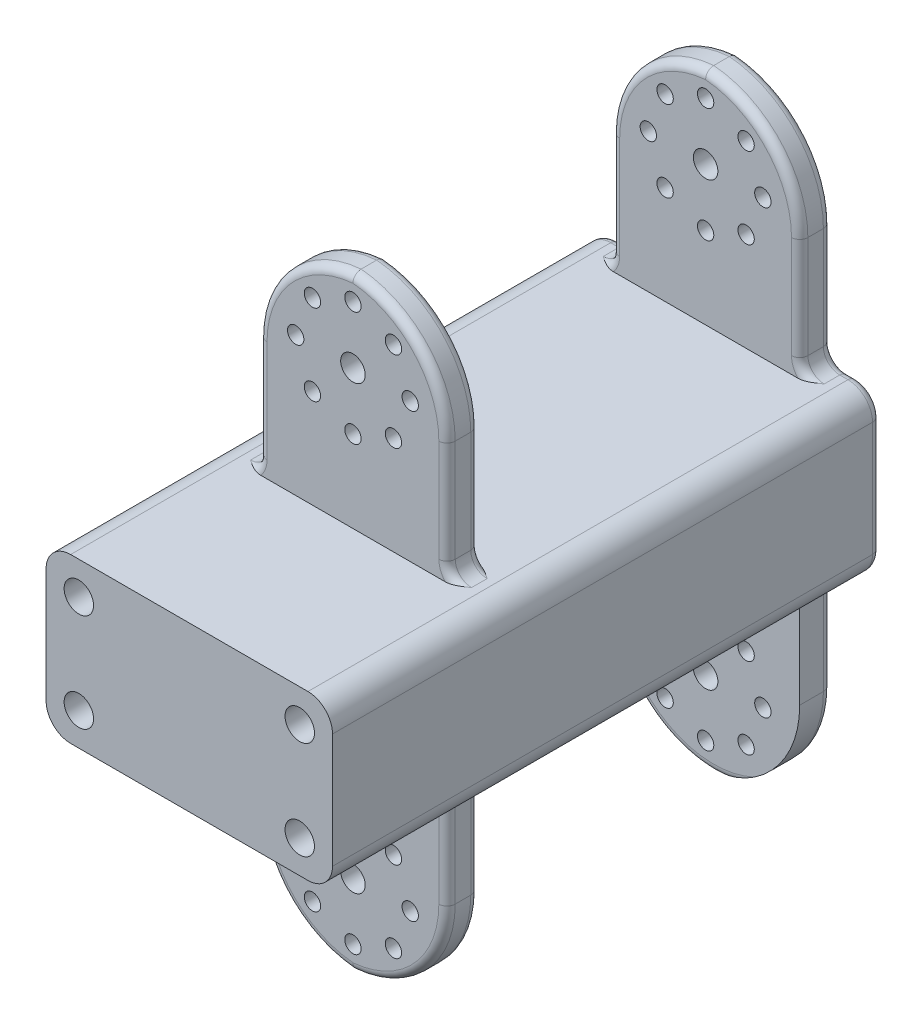
SolidWorks part; units mm, degrees
ref_plane "Front Plane" through (0, 0, 0) normal (0, 0, 1) x (1, 0, 0)
ref_plane "Top Plane" through (0, 0, 0) normal (0, 1, 0) x (1, 0, 0)
ref_plane "Right Plane" through (0, 0, 0) normal (1, 0, 0) x (0, 0, -1)
sketch "Sketch1" plane through (0, 0, 0) normal (0, 1, 0) x (1, 0, 0)
  line L1 (-12.5, 24.5) -> (22.5, 24.5)
  line L2 (-12.5, 24.5) -> (-12.5, -22.5)
  line L3 (-12.5, -22.5) -> (22.5, -22.5)
  line L4 (22.5, 24.5) -> (22.5, -22.5)
  dimension "D1" = 47
  dimension "D2" = 35
  dimension "D3" = 22.5
  dimension "D4" = 22.5
extrude "Boss-Extrude1" add sketch "Sketch1" along normal blind 20
sketch "Sketch2" plane through (0, 0, 0) normal (0, -1, 0) x (1, 0, 0)
  line L0 (22.5, 22.5) -> (22.5, -24.5) construction
  line L6 (-6.5, -24.5) -> (16.5, -24.5)
  line L7 (-6.5, -24.5) -> (-6.5, -20.6)
  line L8 (-6.5, -20.6) -> (16.5, -20.6)
  line L9 (16.5, -24.5) -> (16.5, -20.6)
  line L13 (22.5, -24.5) -> (-12.5, -24.5) construction
  line L15 (-6.5, 18.6) -> (16.5, 18.6)
  line L16 (-6.5, 18.6) -> (-6.5, 22.5)
  line L17 (-6.5, 22.5) -> (16.5, 22.5)
  line L18 (16.5, 18.6) -> (16.5, 22.5)
  line L19 (-12.5, 22.5) -> (22.5, 22.5) construction
  dimension "D1" = 3.9
  dimension "D2" = 23
  dimension "D3" = 6
sketch "Sketch3" plane through (0, 20, 0) normal (0, 1, 0) x (1, 0, 0)
  line L0 (-12.5, 24.5) -> (-12.5, -22.5) construction
  line L1 (-12.5, -12) -> (22.5, -12)
  line L2 (-12.5, -12) -> (-12.5, -15)
  line L3 (-12.5, -15) -> (22.5, -15)
  line L4 (22.5, -12) -> (22.5, -15)
  line L5 (22.5, -22.5) -> (22.5, 24.5) construction
  line L6 (-12.5, -22.5) -> (22.5, -22.5) construction
  line L7 (-12.5, 16) -> (22.5, 16)
  line L8 (-12.5, 16) -> (-12.5, 13)
  line L9 (-12.5, 13) -> (22.5, 13)
  line L10 (22.5, 16) -> (22.5, 13)
  dimension "D1" = 25
  dimension "D2" = 3
  dimension "D3" = 7.5
sketch "Sketch7" plane through (0, 0, 22.5) normal (0, 0, 1) x (1, 0, 0)
  line L0 (22.5, 20) -> (22.5, 0) construction
  line L1 (-12.5, 0) -> (22.5, 0)
  line L2 (-12.5, 0) -> (-12.5, 20)
  line L3 (-12.5, 20) -> (22.5, 20)
  line L4 (22.5, 0) -> (22.5, 20)
  line L5 (-12.5, 20) -> (-12.5, 0) construction
  line L6 (-12.5, 20) -> (22.5, 20) construction
  dimension "D1" = 20
  dimension "D2" = 20
extrude "Boss-Extrude3" add sketch "Sketch7" along normal blind 20
sketch "Sketch8" plane through (0, 0, 42.5) normal (0, 0, 1) x (1, 0, 0)
  line L1 (-17.5, 38) -> (27.5, 38)
  line L2 (-17.5, 38) -> (-17.5, -18)
  line L3 (-17.5, -18) -> (27.5, -18)
  line L4 (27.5, 38) -> (27.5, -18)
  line L6 (-12.5, 20) -> (22.5, 20) construction
  line L7 (22.5, 0) -> (22.5, 20) construction
  dimension "D1" = 18
  dimension "D2" = 38
  dimension "D3" = 45
  dimension "D4" = 5
extrude "Boss-Extrude4" [suppressed] add sketch "Sketch8" along normal blind 5
sketch "Sketch9" [suppressed] plane through (0, 0, 47.5) normal (0, 0, 1) x (1, 0, 0)
  line L0 (-17.5, 38) -> (-17.5, -18) construction
  line L1 (27.5, 38) -> (-17.5, 38) construction
  line L2 (-17.5, -18) -> (27.5, -18) construction
  line L3 (27.5, -18) -> (27.5, 38) construction
  circle A0 centre (-10, 33) radius 1.8
  circle A1 centre (20, 33) radius 1.8
  circle A2 centre (20, -13) radius 1.8
  circle A3 centre (-10, -13) radius 1.8
  dimension "D2" = 3.6
  dimension "D4" = 3.6
  dimension "D5" = 3.6
  dimension "D6" = 3.6
  dimension "D1" = 7.5
  dimension "D3" = 5
  dimension "D7" = 5
  dimension "D8" = 7.5
extrude "Cut-Extrude2" [suppressed] cut sketch "Sketch9" against normal blind 3
extrude "Boss-Extrude5" add sketch "Sketch2" along normal blind 27
ref_plane "Plane1" through (0, 10, 0) normal (0, 1, 0) x (1, 0, 0)
sketch "Sketch10" plane through (0, 0, -24.5) normal (0, 0, -1) x (-1, 0, 0)
  line L0 (-5, -27) -> (-5, -17)
  line L1 (6.5, -27) -> (-16.5, -27) construction
  circle A0 centre (-5, -17) radius 1.5
  circle A1 centre (-5, -17) radius 7
  circle A2 centre (-5, -10) radius 1
  circle A3 centre (-0.0503, -12.0503) radius 1
  circle A4 centre (2, -17) radius 1
  circle A5 centre (-0.0503, -21.9497) radius 1
  circle A6 centre (-5, -24) radius 1
  circle A7 centre (-9.9497, -21.9497) radius 1
  circle A8 centre (-12, -17) radius 1
  circle A9 centre (-9.9497, -12.0503) radius 1
  point P24 (-5, -17)
  dimension "D2" = 3
  dimension "D3" = 14
  dimension "D4" = 2
  dimension "D1" = 10
  dimension "D6" = 7
  dimension "D5" = 8
extrude "Cut-Extrude3" cut sketch "Sketch10" against normal blind 50
mirror "Mirror3" about plane through (0, 10, 0) normal (0, 1, 0) of "Cut-Extrude3", "Boss-Extrude5"
fillet "Fillet1" radius 12.5 8 edges at (-6.5, 47, 20.55) (16.5, 47, 20.55) (-6.5, 47, -22.55) (16.5, 47, -22.55) (-6.5, -27, -22.55) (16.5, -27, -22.55) (-6.5, -27, 20.55) (16.5, -27, 20.55)
fillet "Fillet2" [suppressed] radius 3
fillet "Fillet3" radius 3 4 edges at (-12.5, 0, 9) (-12.5, 20, 9) (22.5, 20, 9) (22.5, 0, 9)
fillet "Fillet4" radius 2 8 edges at (-6.5, 0, -22.55) (16.5, 0, -22.55) (16.5, 0, 20.55) (-6.5, 0, 20.55) (-6.5, 20, 20.55) (16.5, 20, 20.55) (16.5, 20, -22.55) (-6.5, 20, -22.55)
fillet "Fillet5" radius 1 55 edges at (-7.0858, 20.5858, -20.6) (-6.5, 28.25, -20.6) (13.1856, -22.9779, 22.5) (17.0858, -0.5858, 22.5) (13.1856, -22.9779, 18.6) (17.0858, -0.5858, 18.6) (-7.0858, -0.5858, 18.6) (-6.5, -8.25, 18.6) (-7.0858, -0.5858, 22.5) (-6.5, -8.25, 22.5) (-3.1856, 42.9779, 18.6) (-7.0858, 20.5858, 18.6) (-3.1856, 42.9779, 22.5) (-7.0858, 20.5858, 22.5) (17.0858, 20.5858, 18.6) (16.5, 28.25, 18.6) (17.0858, 20.5858, 22.5) (16.5, 28.25, 22.5) (17.0858, 20.5858, -20.6) (16.5, 28.25, -20.6) (13.1856, 42.9779, -24.5) (13.1856, -22.9779, -24.5) (16.5, -8.25, -24.5) (17.0858, -0.5858, -24.5) (19, 0, -24.5) (21.6213, 0.8787, -24.5) (22.5, 10, -24.5) (21.6213, 19.1213, -24.5) (19, 20, -24.5) (17.0858, 20.5858, -24.5) (-3.1856, -22.9779, -24.5) (-3.1856, 42.9779, -24.5) (-6.5, 28.25, -24.5) (-7.0858, 20.5858, -24.5) (-9, 20, -24.5) (-11.6213, 19.1213, -24.5) (-12.5, 10, -24.5) (-11.6213, 0.8787, -24.5) (-9, 0, -24.5) (-7.0858, -0.5858, -24.5) (-7.0858, -0.5858, -20.6) (-6.5, -8.25, -20.6) (-3.1856, 42.9779, -20.6) (16.5, -8.25, 22.5) (16.5, -8.25, 18.6) (-3.1856, -22.9779, 18.6) (-3.1856, -22.9779, 22.5) (-6.5, 28.25, 18.6) (-6.5, 28.25, 22.5) (13.1856, 42.9779, 18.6) (13.1856, 42.9779, 22.5) (13.1856, 42.9779, -20.6) (16.5, 28.25, -24.5) (-6.5, -8.25, -24.5) (-3.1856, -22.9779, -20.6)
sketch "Sketch11" plane through (0, 0, 42.5) normal (0, 0, 1) x (1, 0, 0)
  line L0 (24.75, 0) -> (-24.75, 0) construction
  line L1 (-12.5, 17) -> (-12.5, 3) construction
  line L2 (19.5, 20) -> (-9.5, 20) construction
  line L3 (22.5, 3) -> (22.5, 17) construction
  circle A0 centre (-8.5, 4) radius 1.8
  circle A1 centre (18.5, 4) radius 1.8
  circle A2 centre (18.5, 16) radius 1.8
  circle A3 centre (-8.5, 16) radius 1.8
  dimension "D1" = 3.6
  dimension "D2" = 4
  dimension "D3" = 4
  dimension "D6" = 4
  dimension "D7" = 4
  dimension "D8" = 4
  dimension "D4" = 2
  dimension "D5" = 2
extrude "Cut-Extrude4" cut sketch "Sketch11" against normal blind 3
